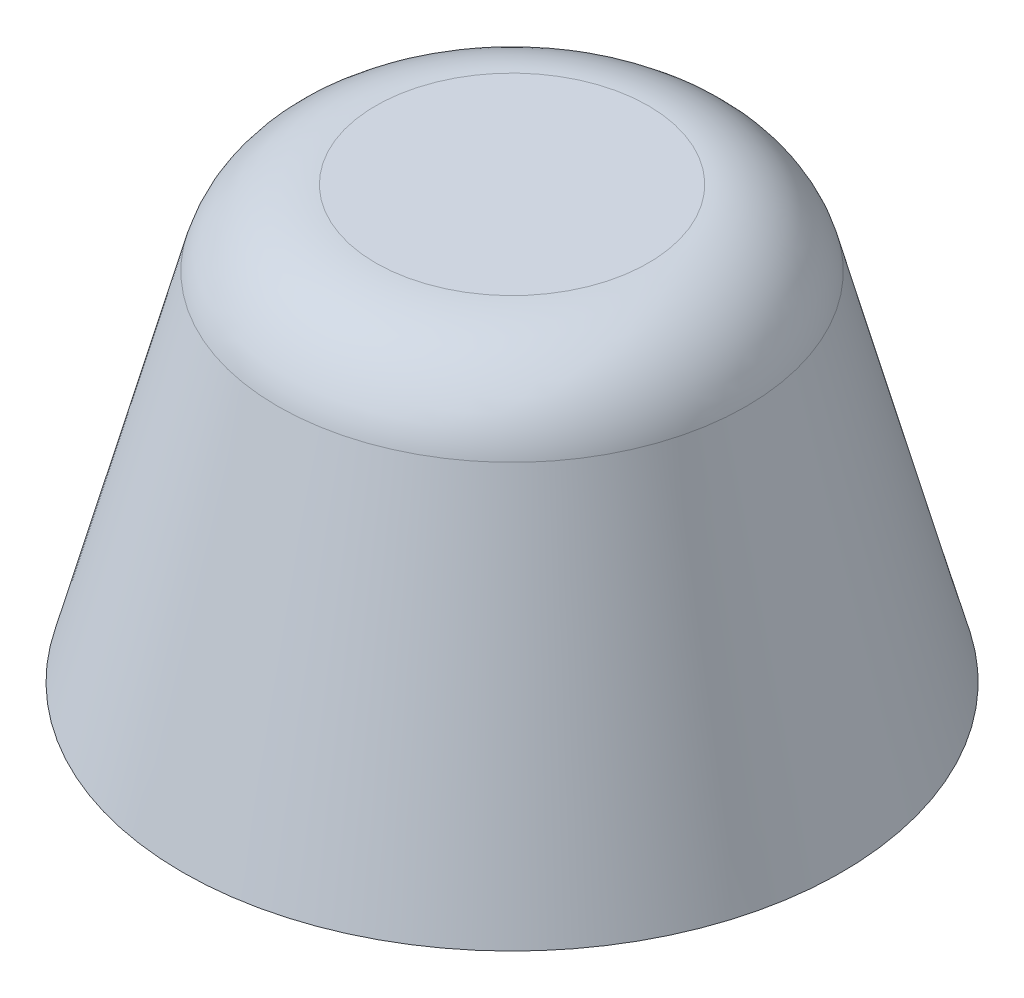
SolidWorks part; units mm, degrees
ref_plane "Front Plane" through (0, 0, 0) normal (0, 0, 1) x (1, 0, 0)
ref_plane "Top Plane" through (0, 0, 0) normal (0, 1, 0) x (1, 0, 0)
ref_plane "Right Plane" through (0, 0, 0) normal (1, 0, 0) x (0, 0, -1)
sketch "Sketch1" plane through (0, 0, 0) normal (0, 1, 0) x (1, 0, 0)
  circle A0 centre (0, 0) radius 6.5
  dimension "D1" = 13
extrude "Boss-Extrude1" add sketch "Sketch1" along normal blind 8.5 draft 15
sketch "Sketch2" plane through (0, 0, 0) normal (0, -1, 0) x (1, 0, 0)
  circle A0 centre (0, 0) radius 5.1
  dimension "D1" = 10.2
extrude "Cut-Extrude1" cut sketch "Sketch2" against normal blind 2.25
fillet "Fillet1" radius 2 1 edges at (0, 8.5, 4.2224)
shell "Shell2" thickness 1.15 removed face at (0, 2.25, -5.1)
